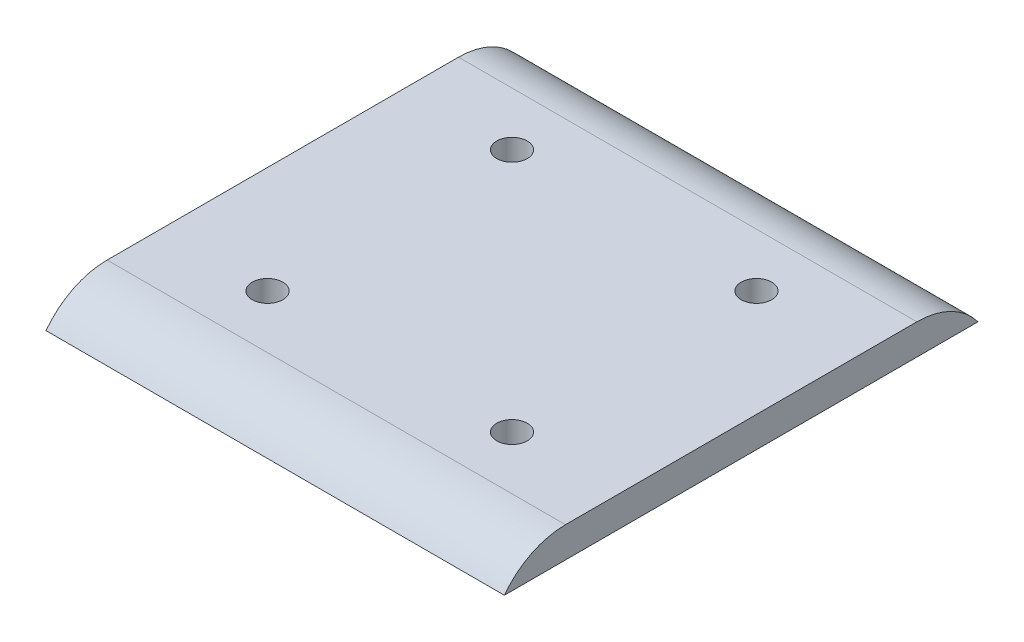
SolidWorks part; units mm, degrees
ref_plane "Front Plane" through (0, 0, 0) normal (0, 0, 1) x (1, 0, 0)
ref_plane "Top Plane" through (0, 0, 0) normal (0, 1, 0) x (1, 0, 0)
ref_plane "Right Plane" through (0, 0, 0) normal (1, 0, 0) x (0, 0, -1)
sketch "Sketch1" plane through (0, 0, 0) normal (0, 1, 0) x (1, 0, 0)
  line L1 (-17.3267, 10.9901) -> (12.6733, 10.9901)
  line L2 (-17.3267, 10.9901) -> (-17.3267, -20.0099)
  line L3 (-17.3267, -20.0099) -> (12.6733, -20.0099)
  line L4 (12.6733, 10.9901) -> (12.6733, -20.0099)
  dimension "D1" = 30
  dimension "D2" = 31
extrude "Boss-Extrude1" add sketch "Sketch1" along normal blind 2
sketch "Sketch2" plane through (0, 0, 0) normal (0, 1, 0) x (1, 0, 0)
  line L0 (12.6733, 10.9901) -> (-17.3267, 10.9901) construction
  line L1 (-17.3267, 10.9901) -> (-17.3267, -20.0099) construction
  line L2 (12.6733, -20.0099) -> (12.6733, 10.9901) construction
  circle A0 centre (-10.3267, 3.4901) radius 1
  circle A1 centre (-10.3267, -12.5099) radius 1
  circle A2 centre (5.6733, 3.4901) radius 1
  circle A3 centre (5.6733, -12.5099) radius 1
  dimension "D1" = 7.5
  dimension "D3" = 16
  dimension "D5" = 16
  dimension "D2" = 7
  dimension "D4" = 7
  dimension "D6" = 16
  dimension "D7" = 7.5
  dimension "D8" = 16
  dimension "D9" = 7
extrude "Cut-Extrude2" cut sketch "Sketch2" along normal blind 4
fillet "Fillet2" radius 5 1 edges at (-2.3267, 2, 20.0099)
fillet "Fillet3" radius 5 1 edges at (-2.3267, 2, -10.9901)
